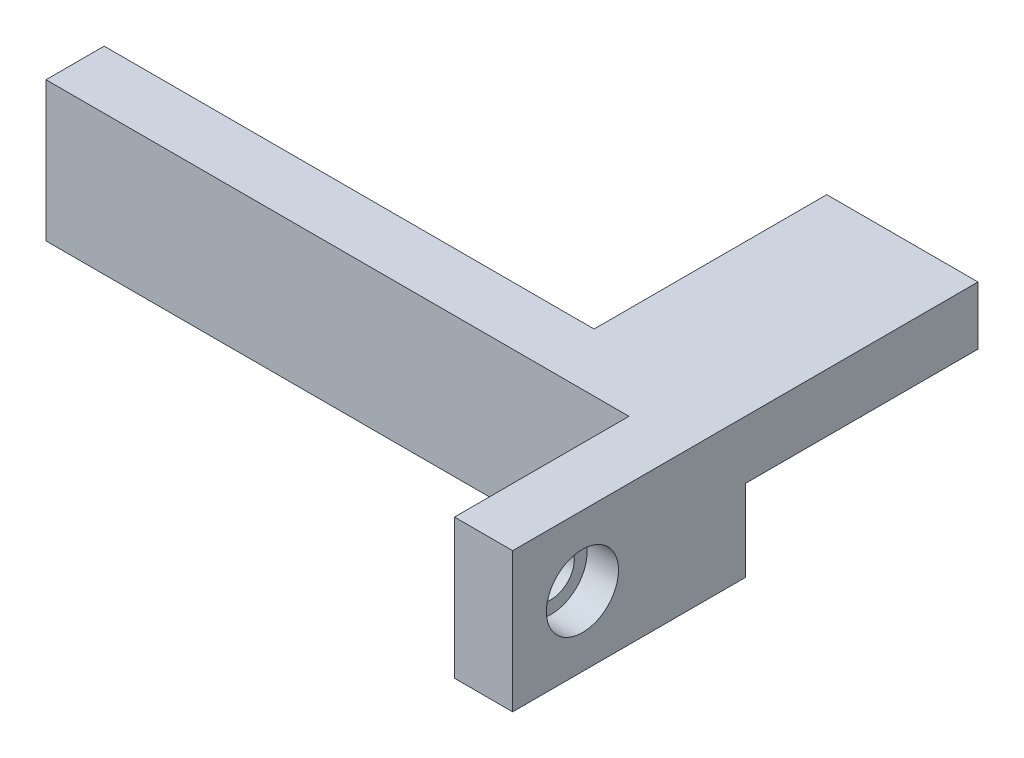
SolidWorks part; units mm, degrees
ref_plane "前视基准面" through (0, 0, 0) normal (0, 0, 1) x (1, 0, 0)
ref_plane "上视基准面" through (0, 0, 0) normal (0, 1, 0) x (1, 0, 0)
ref_plane "右视基准面" through (0, 0, 0) normal (1, 0, 0) x (0, 0, -1)
other "Configuration Table"
sketch "草图1" plane through (0, 0, 0) normal (0, 1, 0) x (1, 0, 0)
  line L1 (0, 0) -> (-42.1106, 0)
  line L2 (0, 0) -> (0, 5)
  line L3 (0, 5) -> (-42.1106, 5)
  line L4 (-42.1106, 0) -> (-42.1106, 5)
  dimension "D1" = 5
extrude "凸台-拉伸1" add sketch "草图1" along normal blind 5
sketch "草图2" plane through (0, 0, 0) normal (0, 0, -1) x (-1, 0, 0)
  line L0 (0, 0) -> (42.1106, 0) construction
  line L1 (0, 5) -> (-13, 5)
  line L2 (0, 5) -> (0, 0)
  line L3 (0, 0) -> (-13, 0)
  line L4 (-13, 5) -> (-13, 0)
  line L6 (-13, 5) -> (-8, 5)
  line L7 (-13, 5) -> (-13, 0)
  line L8 (-13, 0) -> (-8, 0)
  line L9 (-8, 5) -> (-8, 0)
  dimension "D1" = 13
  dimension "D2" = 5
extrude "凸台-拉伸2" add sketch "草图2" along normal blind 25 contours L1 L4 L3 L2
extrude "凸台-拉伸3" add sketch "草图2<3>" against normal blind 15 contours L1 L9 L3 L4 region at (10.5, 2.5, 0)
sketch "草图2<3>" plane through (0, 0, 0) normal (0, 0, -1) x (-1, 0, 0) same geometry as "草图2"
sketch "草图3" plane through (0, 0, 0) normal (0, -1, 0) x (1, 0, 0)
  line L0 (13, -25) -> (13, 15) construction
  line L1 (-42.1106, 0) -> (13, 0)
  line L2 (-42.1106, 0) -> (-42.1106, -5)
  line L3 (-42.1106, -5) -> (13, -5)
  line L4 (13, 0) -> (13, -5)
  line L5 (0, -5) -> (-42.1106, -5) construction
  line L7 (13, 0) -> (8, 0)
  line L8 (13, 0) -> (13, 15)
  line L9 (13, 15) -> (8, 15)
  line L10 (8, 0) -> (8, 15)
extrude "凸台-拉伸4" add sketch "草图3" along normal blind 7 contours L4 L3 L2 L1 | L7 L10 L9 L8
sketch "草图4" plane through (13, 0, 0) normal (1, 0, 0) x (0, 0, -1)
  line L0 (-15, 5) -> (-15, -7) construction
  circle A0 centre (-9, -1) radius 3.1
  circle A1 centre (-9, -1) radius 2
  point P5 (-15, -1)
  dimension "D2" = 6.2
  dimension "D3" = 4
  dimension "D1" = 6
extrude "切除-拉伸1" cut sketch "草图4" against normal through all contours A1
extrude "切除-拉伸2" cut sketch "草图4<3>" against normal blind 2.7 contours A0
sketch "草图4<3>" plane through (13, 0, 0) normal (1, 0, 0) x (0, 0, -1) same geometry as "草图4"
